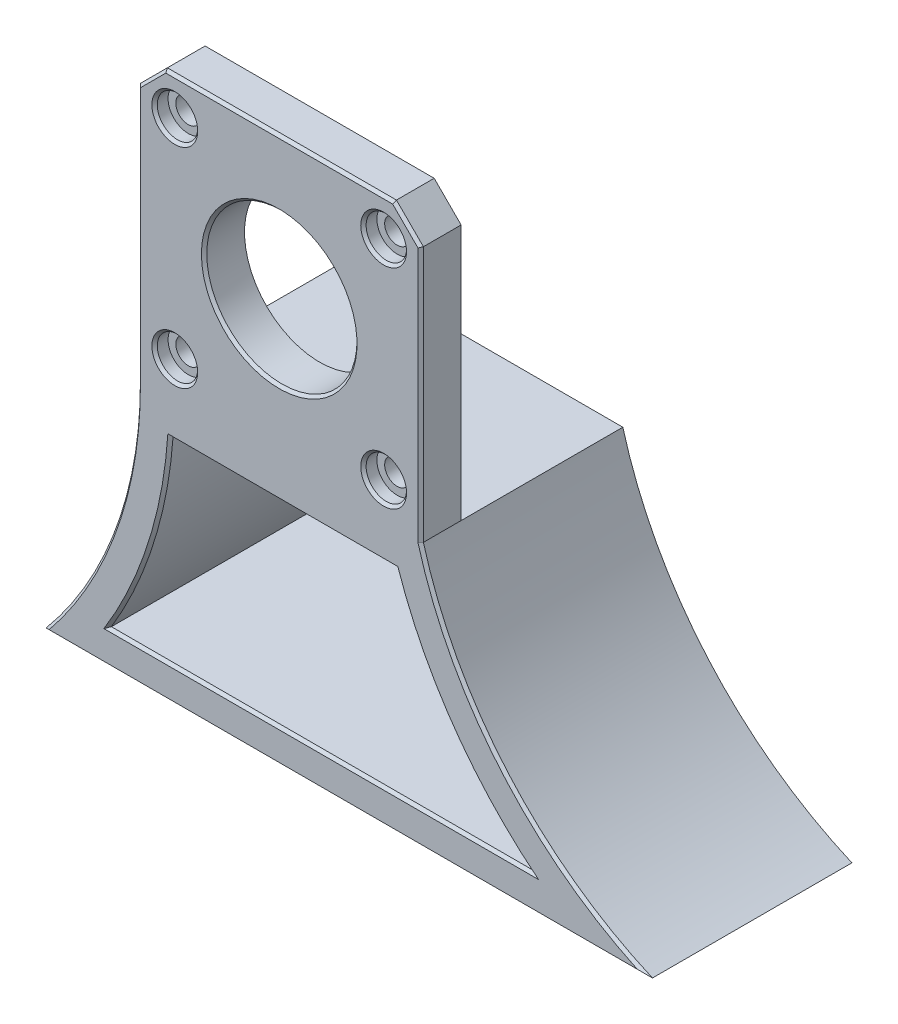
SolidWorks part; units mm, degrees
ref_plane "Front Plane" through (0, 0, 0) normal (0, 0, 1) x (1, 0, 0)
ref_plane "Top Plane" through (0, 0, 0) normal (0, 1, 0) x (1, 0, 0)
ref_plane "Right Plane" through (0, 0, 0) normal (1, 0, 0) x (0, 0, -1)
sketch "Sketch1" plane through (0, 0, 0) normal (0, 0, 1) x (1, 0, 0)
  line L1 (-21, -21) -> (21, -21)
  line L2 (-21, -21) -> (-21, 21)
  line L3 (-21, 21) -> (21, 21)
  line L4 (21, -21) -> (21, 21)
  line L5 (-21, -21) -> (21, 21) construction
  line L6 (-21, 21) -> (21, -21) construction
  line L7 (-15.5, -15.5) -> (15.5, -15.5) construction
  line L8 (-15.5, -15.5) -> (-15.5, 15.5) construction
  line L9 (-15.5, 15.5) -> (15.5, 15.5) construction
  line L10 (15.5, -15.5) -> (15.5, 15.5) construction
  line L11 (-15.5, -15.5) -> (15.5, 15.5) construction
  line L12 (-15.5, 15.5) -> (15.5, -15.5) construction
  circle A0 centre (0, 0) radius 11.15
  circle A1 centre (15.5, 15.5) radius 1.85
  circle A2 centre (-15.5, 15.5) radius 1.85
  circle A3 centre (-15.5, -15.5) radius 1.85
  circle A4 centre (15.5, -15.5) radius 1.85
  point P0 (0, 0)
  dimension "D2" = 22.3
  dimension "D4" = 3.7
  dimension "D1" = 42
  dimension "D3" = 31
extrude "Boss-Extrude1" add sketch "Sketch1" against normal blind 6
sketch "Sketch2" plane through (0, 0, 0) normal (0, 0, 1) x (1, 0, 0)
  line L0 (-35, -60) -> (55, -60)
  line L1 (-21, -21) -> (21, -21)
  arc A0 (-21, -21) -> (-35, -60) centre (-80.9981, -21.475) cw
  arc A1 (21, -21) -> (55, -60) centre (78.8065, -4.9251) ccw
  dimension "D3" = 35
  dimension "D4" = 60
  dimension "D5" = 60
  dimension "D1" = 90
  dimension "D2" = 60
extrude "Boss-Extrude2" add sketch "Sketch2" against normal blind 30
sketch "Sketch3" plane through (0, 0, -30) normal (0, 0, -1) x (-1, 0, 0)
  line L4 (-37.3638, -55) -> (25.3108, -55)
  line L5 (16.1558, -26) -> (-17.318, -26)
  line L6 (-37.3638, -55) -> (25.3108, -55)
  line L7 (16.1558, -26) -> (-17.318, -26)
  arc A4 (16.1558, -26) -> (25.3108, -55) centre (80.9981, -21.475) ccw
  arc A5 (-37.3638, -55) -> (-17.318, -26) centre (-78.8065, -4.9251) ccw
  arc A6 (16.1558, -26) -> (25.3108, -55) centre (80.9981, -21.475) ccw
  arc A7 (-37.3638, -55) -> (-17.318, -26) centre (-78.8065, -4.9251) ccw
  dimension "D1" = 5
extrude "Cut-Extrude1" cut sketch "Sketch3" against normal through all
sketch "Sketch4" plane through (0, 0, 0) normal (0, 0, 1) x (1, 0, 0)
  circle A0 centre (15.5, 15.5) radius 3
  circle A1 centre (15.5, -15.5) radius 3
  circle A2 centre (-15.5, -15.5) radius 3
  circle A3 centre (-15.5, 15.5) radius 3
  dimension "D1" = 6
extrude "Cut-Extrude2" cut sketch "Sketch4" against normal blind 2
chamfer "Chamfer1" distance 4 angle 45 2 edges at (-21, 21, -3) (21, 21, -3)
chamfer "Chamfer2" distance 0.4 angle 45 17 edges at (19, 19, 0) (21, -2, 0) (33.5802, -44.3532, 0) (10, -60, 0) (-24.5264, -41.7469, 0) (-21, -2, 0) (-19, 19, 0) (0, 21, 0) (11.15, 0, 0) (-19.0135, -41.0429, 0) (6.0265, -55, 0) (25.3373, -41.885, 0) (0.5811, -26, 0) (18.5, 15.5, 0) (18.5, -15.5, 0) (-12.5, -15.5, 0) (-12.5, 15.5, 0)
